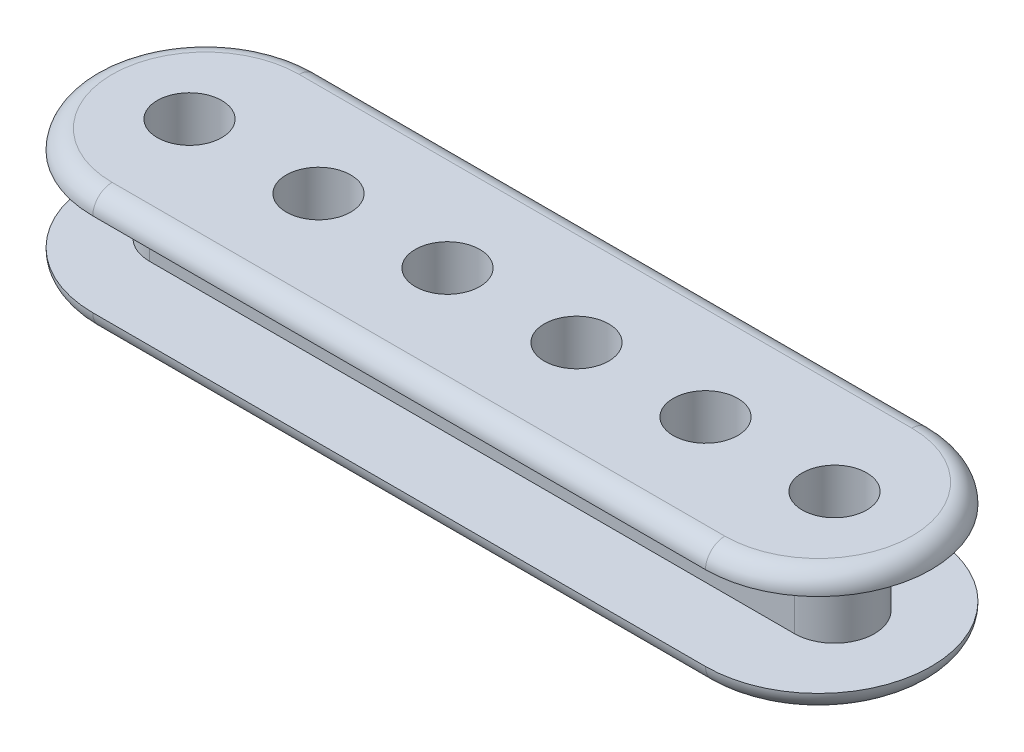
SolidWorks part; units mm, degrees
material "ABS"
ref_plane "Front Plane" through (0, 0, 0) normal (0, 0, 1) x (1, 0, 0)
ref_plane "Top Plane" through (0, 0, 0) normal (0, 1, 0) x (1, 0, 0)
ref_plane "Right Plane" through (0, 0, 0) normal (1, 0, 0) x (0, 0, -1)
sketch "Sketch1" plane through (0, 0, 0) normal (0, 1, 0) x (1, 0, 0)
  line L0 (24.13, 0) -> (-24.13, 0) construction
  line L1 (24.13, -8.89) -> (-24.13, -8.89)
  line L2 (24.13, 8.89) -> (-24.13, 8.89)
  arc A0 (24.13, -8.89) -> (24.13, 8.89) centre (24.13, 0) ccw
  arc A1 (-24.13, 8.89) -> (-24.13, -8.89) centre (-24.13, 0) ccw
  point P2 (0, 0)
  point P8 (-33.02, 0)
  point P9 (33.02, 0)
  dimension "D1" = 17.78
  dimension "D2" = 66.04
extrude "Boss-Extrude1" add sketch "Sketch1" along normal blind 1.524
sketch "Sketch2" plane through (0, 1.524, 0) normal (0, 1, 0) x (1, 0, 0)
  line L0 (-33.02, 0) -> (33.02, 0) construction
  line L1 (-25.4, 3.1496) -> (25.4, 3.1496)
  line L2 (-24.13, -8.89) -> (24.13, -8.89) construction
  line L3 (25.4, 1.524) -> (-25.4, 1.524)
  line L4 (25.4, 1.524) -> (25.4, -1.524)
  line L5 (25.4, -1.524) -> (-25.4, -1.524)
  line L6 (-25.4, 1.524) -> (-25.4, -1.524)
  line L7 (25.4, 1.524) -> (-25.4, -1.524) construction
  line L8 (25.4, -1.524) -> (-25.4, 1.524) construction
  line L9 (-25.4, -3.1496) -> (25.4, -3.1496)
  arc A0 (-24.13, 8.89) -> (-24.13, -8.89) centre (-24.13, 0) ccw construction
  arc A1 (24.13, -8.89) -> (24.13, 8.89) centre (24.13, 0) ccw construction
  circle A2 centre (-25.4, 0) radius 3.1496
  circle A3 centre (-15.24, 0) radius 3.1496
  circle A4 centre (-5.08, 0) radius 3.1496
  circle A5 centre (5.08, 0) radius 3.1496
  circle A6 centre (15.24, 0) radius 3.1496
  circle A7 centre (25.4, 0) radius 3.1496
  circle A8 centre (-25.4, 0) radius 1.27
  circle A9 centre (-15.24, 0) radius 1.27
  circle A10 centre (-5.08, 0) radius 1.27
  circle A11 centre (5.08, 0) radius 1.27
  circle A12 centre (15.24, 0) radius 1.27
  circle A13 centre (25.4, 0) radius 1.27
  point P10 (0, 0)
  point P30 (0, -8.89)
  dimension "D1" = 6.2992
  dimension "D3" = 6
  dimension "D7" = 2.54
  dimension "D2" = 7.62
  dimension "D4" = 8.89
  dimension "D5" = 7.366
  dimension "D6" = 50.8
  dimension "D8" = 6
extrude "Boss-Extrude2" add sketch "Sketch2" along normal blind 6.604 contours A8 L6 L3 A2 L5 | A3 L1 A2 L3 | A3 L3 A2 L5 | A8 L6 L5 A2 L3 | A3 L5 A2 L9 | A3 L5 | L5 A3 L3 A9 | L3 A3 | A4 L1 A3 L3 | A4 L3 A3 L5 | A4 L5 A3 L9 | A4 L5 | L5 A4 L3 A10 | L3 A4 | A5 L1 A4 L3 | A5 L3 A4 L5 | A5 L5 A4 L9 | A5 L5 | L5 A5 L3 A11 | L3 A5 | A6 L1 A5 L3 | A6 L3 A5 L5 | A6 L5 A5 L9 | A6 L5 | L5 A6 L3 A12 | L3 A6 | A7 L1 A6 L3 | A7 L5 A6 L9 | A7 L3 A6 L5 | A13 L4 L5 A7 L3 | A13 L4 L3 A7 L5 region at (-23.8439, 1.524, -2.6386) region at (-20.32, 1.524, -2.4283) region at (-10.16, 1.524, -2.4283) region at (-15.24, 1.524, -2.1912) region at (-20.32, 1.524, 2.4283) region at (-23.5172, 1.524, 0) region at (-20.32, 1.524, 0) region at (0, 1.524, -2.4283) region at (-5.08, 1.524, -2.1912) region at (-12.2581, 1.524, -0.7695) region at (-10.16, 1.524, 0) region at (-10.16, 1.524, 2.4283) region at (-15.24, 1.524, 2.1912) region at (10.16, 1.524, -2.4283) region at (5.08, 1.524, -2.1912) region at (-2.0981, 1.524, -0.7695) region at (0, 1.524, 0) region at (0, 1.524, 2.4283) region at (-5.08, 1.524, 2.1912) region at (20.32, 1.524, -2.4283) region at (15.24, 1.524, -2.1912) region at (8.0619, 1.524, -0.7695) region at (10.16, 1.524, 0) region at (10.16, 1.524, 2.4283) region at (5.08, 1.524, 2.1912) region at (27.566, 1.524, -2.166) region at (18.2219, 1.524, -0.7695) region at (20.32, 1.524, 0) region at (20.32, 1.524, 2.4283) region at (15.24, 1.524, 2.1912) region at (23.5172, 1.524, 0)
sketch "Sketch3" plane through (0, 8.128, 0) normal (0, 1, 0) x (1, 0, 0)
  line L0 (-24.13, -8.89) -> (24.13, -8.89) construction
  line L1 (24.13, 8.89) -> (-24.13, 8.89) construction
  line L2 (-24.13, -8.89) -> (24.13, -8.89)
  line L3 (24.13, 8.89) -> (-24.13, 8.89)
  arc A0 (24.13, -8.89) -> (24.13, 8.89) centre (24.13, 0) ccw construction
  arc A1 (-24.13, 8.89) -> (-24.13, -8.89) centre (-24.13, 0) ccw construction
  arc A2 (24.13, -8.89) -> (24.13, 8.89) centre (24.13, 0) ccw
  arc A3 (-24.13, 8.89) -> (-24.13, -8.89) centre (-24.13, 0) ccw
extrude "Boss-Extrude3" add sketch "Sketch3" along normal blind 1.524
fillet "Fillet1" radius 1.524 8 edges at (33.02, 0, 0) (0, 0, -8.89) (0, 0, 8.89) (-33.02, 0, 0) (33.02, 9.652, 0) (0, 9.652, 8.89) (0, 9.652, -8.89) (-33.02, 9.652, 0)
extrude "Cut-Extrude1" cut sketch "Sketch2<3>" against normal through all both and the other way through all contours A8 | A9 | A10 | A11 | A12 | A13
sketch "Sketch2<3>" plane through (0, 1.524, 0) normal (0, 1, 0) x (1, 0, 0) same geometry as "Sketch2"
sketch "Sketch4" plane through (0, 9.652, 0) normal (0, 1, 0) x (1, 0, 0)
  circle A0 centre (-25.4, 0) radius 2.54
  circle A1 centre (-15.24, 0) radius 2.54
  circle A2 centre (-5.08, 0) radius 2.54
  circle A3 centre (5.08, 0) radius 2.54
  circle A4 centre (15.24, 0) radius 2.54
  circle A5 centre (25.4, 0) radius 2.54
  dimension "D1" = 5.08
  dimension "D2" = 6
extrude "Cut-Extrude2" cut sketch "Sketch4" against normal through all and the other way through all
